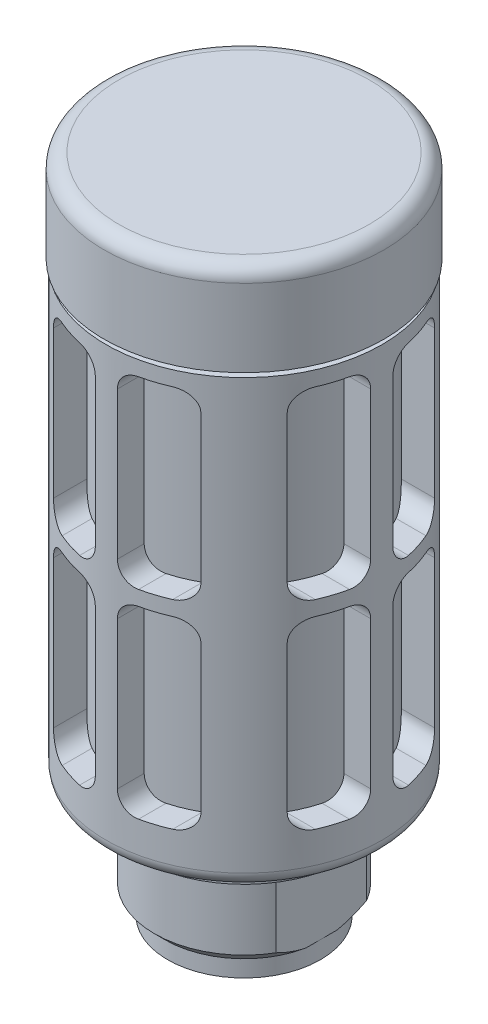
SolidWorks part; units mm, degrees
ref_plane "Front Plane" through (0, 0, 0) normal (0, 0, 1) x (1, 0, 0)
ref_plane "Top Plane" through (0, 0, 0) normal (0, 1, 0) x (1, 0, 0)
ref_plane "Right Plane" through (0, 0, 0) normal (1, 0, 0) x (0, 0, -1)
ref_plane "Plane1" through (0, 0, 0) normal (0, 0, 1) x (1, 0, 0)
sketch "Sketch1" plane through (0, 0, 0) normal (0, 0, 1) x (1, 0, 0)
  line L0 (0, 34.9) -> (-6.05, 34.9)
  line L1 (-6.05, 34.9) -> (-6.05, 7.8)
  line L2 (-6.05, 7.8) -> (-3.2, 7.8)
  line L3 (-3.2, 7.8) -> (-3.2, 0.4)
  line L4 (-3.2, 0.4) -> (-3.6, 0)
  line L5 (-3.6, 0) -> (-4.15, 0)
  line L6 (-4.15, 0) -> (-4.15, 1)
  line L7 (-4.15, 1) -> (-4.283, 1)
  line L8 (-4.283, 1) -> (-4.864, 1.581)
  line L9 (-4.864, 1.581) -> (-4.864, 5.5)
  line L10 (-4.864, 5.5) -> (-5.7, 5.5)
  line L11 (-5.7, 5.5) -> (-5.7, 6.1)
  line L12 (-6.1, 6.5) -> (-6.7, 6.5)
  line L13 (-7.5, 7.3) -> (-7.5, 30.6)
  line L14 (-7.5, 30.6) -> (-7, 30.6)
  line L15 (-6.8, 30.8) -> (-6.8, 30.9)
  line L16 (-6.8, 30.9) -> (-7.6, 30.9)
  line L17 (-7.6, 30.9) -> (-7.6, 35.1)
  line L18 (-6.8, 35.9) -> (0, 35.9)
  line L19 (0, 35.9) -> (0, 34.9)
  line L20 (0, 35.9) -> (0, 0) construction
  arc A0 (-5.7, 6.1) -> (-6.1, 6.5) centre (-6.1, 6.1) ccw
  arc A1 (-6.7, 6.5) -> (-7.5, 7.3) centre (-6.7, 7.3) cw
  arc A2 (-7, 30.6) -> (-6.8, 30.8) centre (-7, 30.8) ccw
  arc A3 (-7.6, 35.1) -> (-6.8, 35.9) centre (-6.8, 35.1) cw
revolve "Revolve1" add sketch "Sketch1" angle 360 about L20 reverse direction yes
cosmetic thread "Cosmetic Thread1" parameters "D1"=3.5, "D2"=8.566
ref_plane "Plane2" through (0, 0, 0) normal (0, 0, 1) x (1, 0, 0)
sketch "Sketch2" plane through (0, 0, 0) normal (0, 0, 1) x (1, 0, 0)
  line L0 (1.6, 19.8) -> (3, 19.8)
  line L1 (4, 20.8) -> (4, 28.8)
  line L2 (3, 29.8) -> (1.6, 29.8)
  line L3 (0.6, 28.8) -> (0.6, 20.8)
  arc A0 (0.6, 20.8) -> (1.6, 19.8) centre (1.6, 20.8) ccw
  arc A1 (3, 19.8) -> (4, 20.8) centre (3, 20.8) ccw
  arc A2 (4, 28.8) -> (3, 29.8) centre (3, 28.8) ccw
  arc A3 (1.6, 29.8) -> (0.6, 28.8) centre (1.6, 28.8) ccw
extrude "Cut-Extrude1" cut sketch "Sketch2" against normal blind 20 and the other way blind 20
ref_plane "Plane3" through (0, 0, 0) normal (0, 0, 1) x (1, 0, 0)
sketch "Sketch3" plane through (0, 0, 0) normal (0, 0, 1) x (1, 0, 0)
  line L0 (1.6, 9) -> (3, 9)
  line L1 (4, 10) -> (4, 18)
  line L2 (3, 19) -> (1.6, 19)
  line L3 (0.6, 18) -> (0.6, 10)
  arc A0 (0.6, 10) -> (1.6, 9) centre (1.6, 10) ccw
  arc A1 (3, 9) -> (4, 10) centre (3, 10) ccw
  arc A2 (4, 18) -> (3, 19) centre (3, 18) ccw
  arc A3 (1.6, 19) -> (0.6, 18) centre (1.6, 18) ccw
extrude "Cut-Extrude2" cut sketch "Sketch3" against normal blind 20 and the other way blind 20
ref_plane "Plane4" through (0, 0, 0) normal (0, 0, 1) x (1, 0, 0)
sketch "Sketch4" plane through (0, 0, 0) normal (0, 0, 1) x (1, 0, 0)
  line L0 (-3, 19.8) -> (-1.6, 19.8)
  line L1 (-0.6, 20.8) -> (-0.6, 28.8)
  line L2 (-1.6, 29.8) -> (-3, 29.8)
  line L3 (-4, 28.8) -> (-4, 20.8)
  arc A0 (-4, 20.8) -> (-3, 19.8) centre (-3, 20.8) ccw
  arc A1 (-1.6, 19.8) -> (-0.6, 20.8) centre (-1.6, 20.8) ccw
  arc A2 (-0.6, 28.8) -> (-1.6, 29.8) centre (-1.6, 28.8) ccw
  arc A3 (-3, 29.8) -> (-4, 28.8) centre (-3, 28.8) ccw
extrude "Cut-Extrude3" cut sketch "Sketch4" against normal blind 20 and the other way blind 20
ref_plane "Plane5" through (0, 0, 0) normal (0, 0, 1) x (1, 0, 0)
sketch "Sketch5" plane through (0, 0, 0) normal (0, 0, 1) x (1, 0, 0)
  line L0 (-3, 9) -> (-1.6, 9)
  line L1 (-0.6, 10) -> (-0.6, 18)
  line L2 (-1.6, 19) -> (-3, 19)
  line L3 (-4, 18) -> (-4, 10)
  arc A0 (-4, 10) -> (-3, 9) centre (-3, 10) ccw
  arc A1 (-1.6, 9) -> (-0.6, 10) centre (-1.6, 10) ccw
  arc A2 (-0.6, 18) -> (-1.6, 19) centre (-1.6, 18) ccw
  arc A3 (-3, 19) -> (-4, 18) centre (-3, 18) ccw
extrude "Cut-Extrude4" cut sketch "Sketch5" against normal blind 20 and the other way blind 20
ref_plane "Plane6" through (0, 0, 0) normal (1, 0, 0) x (0, 0, -1)
sketch "Sketch6" plane through (0, 0, 0) normal (1, 0, 0) x (0, 0, -1)
  line L0 (-3, 19.8) -> (-1.6, 19.8)
  line L1 (-0.6, 20.8) -> (-0.6, 28.8)
  line L2 (-1.6, 29.8) -> (-3, 29.8)
  line L3 (-4, 28.8) -> (-4, 20.8)
  arc A0 (-4, 20.8) -> (-3, 19.8) centre (-3, 20.8) ccw
  arc A1 (-1.6, 19.8) -> (-0.6, 20.8) centre (-1.6, 20.8) ccw
  arc A2 (-0.6, 28.8) -> (-1.6, 29.8) centre (-1.6, 28.8) ccw
  arc A3 (-3, 29.8) -> (-4, 28.8) centre (-3, 28.8) ccw
extrude "Cut-Extrude5" cut sketch "Sketch6" against normal blind 20 and the other way blind 20
ref_plane "Plane7" through (0, 0, 0) normal (1, 0, 0) x (0, 0, -1)
sketch "Sketch7" plane through (0, 0, 0) normal (1, 0, 0) x (0, 0, -1)
  line L0 (-3, 9) -> (-1.6, 9)
  line L1 (-0.6, 10) -> (-0.6, 18)
  line L2 (-1.6, 19) -> (-3, 19)
  line L3 (-4, 18) -> (-4, 10)
  arc A0 (-4, 10) -> (-3, 9) centre (-3, 10) ccw
  arc A1 (-1.6, 9) -> (-0.6, 10) centre (-1.6, 10) ccw
  arc A2 (-0.6, 18) -> (-1.6, 19) centre (-1.6, 18) ccw
  arc A3 (-3, 19) -> (-4, 18) centre (-3, 18) ccw
extrude "Cut-Extrude6" cut sketch "Sketch7" against normal blind 20 and the other way blind 20
ref_plane "Plane8" through (0, 0, 0) normal (1, 0, 0) x (0, 0, -1)
sketch "Sketch8" plane through (0, 0, 0) normal (1, 0, 0) x (0, 0, -1)
  line L0 (1.6, 19.8) -> (3, 19.8)
  line L1 (4, 20.8) -> (4, 28.8)
  line L2 (3, 29.8) -> (1.6, 29.8)
  line L3 (0.6, 28.8) -> (0.6, 20.8)
  arc A0 (0.6, 20.8) -> (1.6, 19.8) centre (1.6, 20.8) ccw
  arc A1 (3, 19.8) -> (4, 20.8) centre (3, 20.8) ccw
  arc A2 (4, 28.8) -> (3, 29.8) centre (3, 28.8) ccw
  arc A3 (1.6, 29.8) -> (0.6, 28.8) centre (1.6, 28.8) ccw
extrude "Cut-Extrude7" cut sketch "Sketch8" against normal blind 20 and the other way blind 20
ref_plane "Plane9" through (0, 0, 0) normal (1, 0, 0) x (0, 0, -1)
sketch "Sketch9" plane through (0, 0, 0) normal (1, 0, 0) x (0, 0, -1)
  line L0 (1.6, 9) -> (3, 9)
  line L1 (4, 10) -> (4, 18)
  line L2 (3, 19) -> (1.6, 19)
  line L3 (0.6, 18) -> (0.6, 10)
  arc A0 (0.6, 10) -> (1.6, 9) centre (1.6, 10) ccw
  arc A1 (3, 9) -> (4, 10) centre (3, 10) ccw
  arc A2 (4, 18) -> (3, 19) centre (3, 18) ccw
  arc A3 (1.6, 19) -> (0.6, 18) centre (1.6, 18) ccw
extrude "Cut-Extrude8" cut sketch "Sketch9" against normal blind 20 and the other way blind 20
ref_plane "Plane10" through (0, 0, 0) normal (0, 0, 1) x (1, 0, 0)
sketch "Sketch10" plane through (0, 0, 0) normal (0, 0, 1) x (1, 0, 0)
  line L0 (-6.2, -11.5) -> (6.2, -11.5)
  line L1 (6.2, -11.5) -> (6.2, 5.5)
  line L2 (6.2, 5.5) -> (4.2, 5.5)
  line L3 (4.2, 5.5) -> (4.2, -9.5)
  line L4 (4.2, -9.5) -> (-4.2, -9.5)
  line L5 (-4.2, -9.5) -> (-4.2, 5.5)
  line L6 (-4.2, 5.5) -> (-6.2, 5.5)
  line L7 (-6.2, 5.5) -> (-6.2, -11.5)
extrude "Cut-Extrude9" cut sketch "Sketch10" against normal blind 15 and the other way blind 15
ref_plane "Plane11" through (0, 0, 0) normal (0, 0, 1) x (1, 0, 0)
sketch "Sketch11" plane through (0, 0, 0) normal (0, 0, 1) x (1, 0, 0)
  line L0 (0, 32.2) -> (-2.2, 32.2)
  line L1 (-3.2, 31.2) -> (-3.2, 7.8)
  line L2 (-3.2, 7.8) -> (-6.05, 7.8)
  line L3 (-6.05, 7.8) -> (-6.05, 34.9)
  line L4 (-6.05, 34.9) -> (0, 34.9)
  line L5 (0, 34.9) -> (0, 32.2)
  line L6 (0, 34.9) -> (0, 7.8) construction
  arc A0 (-2.2, 32.2) -> (-3.2, 31.2) centre (-2.2, 31.2) ccw
revolve "Revolve2" add sketch "Sketch11" angle 360 about L6 reverse direction yes
